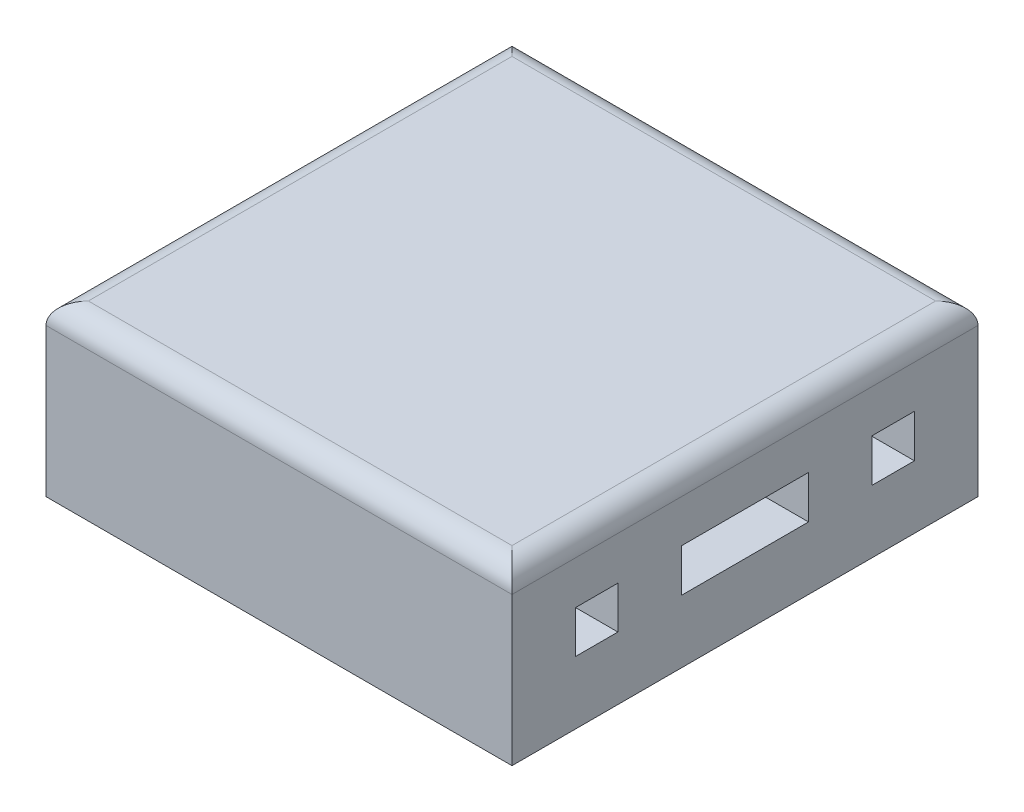
SolidWorks part; units mm, degrees
ref_plane "Front Plane" through (0, 0, 0) normal (0, 0, 1) x (1, 0, 0)
ref_plane "Top Plane" through (0, 0, 0) normal (0, 1, 0) x (1, 0, 0)
ref_plane "Right Plane" through (0, 0, 0) normal (1, 0, 0) x (0, 0, -1)
sketch "Sketch2" plane through (0, 0, 0) normal (0, 1, 0) x (1, 0, 0)
  line L0 (-5.5, -5.5) -> (5.5, -5.5)
  line L1 (0, 0) -> (0, 5.5)
  line L2 (-5.5, -5.5) -> (-5.5, 5.5)
  line L3 (-5.5, 5.5) -> (5.5, 5.5)
  line L4 (5.5, 5.5) -> (5.5, -5.5)
  line L5 (0, 0) -> (-5.5, 0)
  dimension "D1" = 11
  dimension "D2" = 11
  dimension "D3" = 5.5
  dimension "D4" = 5.5
extrude "Boss-Extrude1" add sketch "Sketch2" along normal blind 4 contours L0 L4 L3 L2
sketch "Sketch4" plane through (0, 0, 0) normal (1, 0, 0) x (0, 0, -1)
  line L0 (-4, 1.4828) -> (-4, 2.4828)
  line L1 (-1.5, 2.4957) -> (1.5, 2.4957)
  line L2 (5.5, 4) -> (5.5, 0) construction
  line L3 (-4, 1.4828) -> (-3, 1.4828)
  line L4 (-3, 1.4828) -> (-3, 2.4828)
  line L5 (-3, 2.4828) -> (-4, 2.4828)
  line L6 (-1.5, 1.4828) -> (-1.5, 2.4957)
  line L7 (1.5, 2.4957) -> (1.5, 1.4828)
  line L8 (1.5, 1.4828) -> (-1.5, 1.4828)
  line L9 (-5.5, 4) -> (-5.5, 0) construction
  line L10 (3, 1.4828) -> (3, 2.4957)
  line L11 (3, 2.4957) -> (4, 2.4957)
  line L12 (4, 2.4957) -> (4, 1.4828)
  line L13 (4, 1.4828) -> (3, 1.4828)
  dimension "D1" = 1.5
  dimension "D2" = 1.5
  dimension "D3" = 1.5
  dimension "D4" = 1
  dimension "D5" = 1
  dimension "D6" = 1
  dimension "D7" = 1.5
  dimension "D8" = 3
extrude "Cut-Extrude2" cut sketch "Sketch4" against normal through all both and the other way through all
sketch "Sketch5" plane through (0, 0, 0) normal (0, 1, 0) x (1, 0, 0)
  circle A0 centre (0, 0) radius 2.25
extrude "Cut-Extrude3" cut sketch "Sketch5" against normal through all and the other way blind 2.5
sketch "Sketch8" plane through (0, 0, 0) normal (0, 1, 0) x (1, 0, 0)
  line L0 (0, 0) -> (0, -4.125)
  line L1 (0, 0) -> (0, 4.125)
  circle A0 centre (0, 4.125) radius 0.26
  circle A1 centre (0, -4.125) radius 0.2892
  point P5 (0, 0)
extrude "Cut-Extrude4" cut sketch "Sketch8" along normal blind 0.55 contours A1
extrude "Cut-Extrude5" cut sketch "Sketch8<3>" along normal blind 0.55 contours A0
sketch "Sketch8<3>" plane through (0, 0, 0) normal (0, 1, 0) x (1, 0, 0) same geometry as "Sketch8"
fillet "Fillet2" radius 0.5 4 edges at (0, 4, 5.5) (-5.5, 4, 0) (0, 4, -5.5) (5.5, 4, 0)
